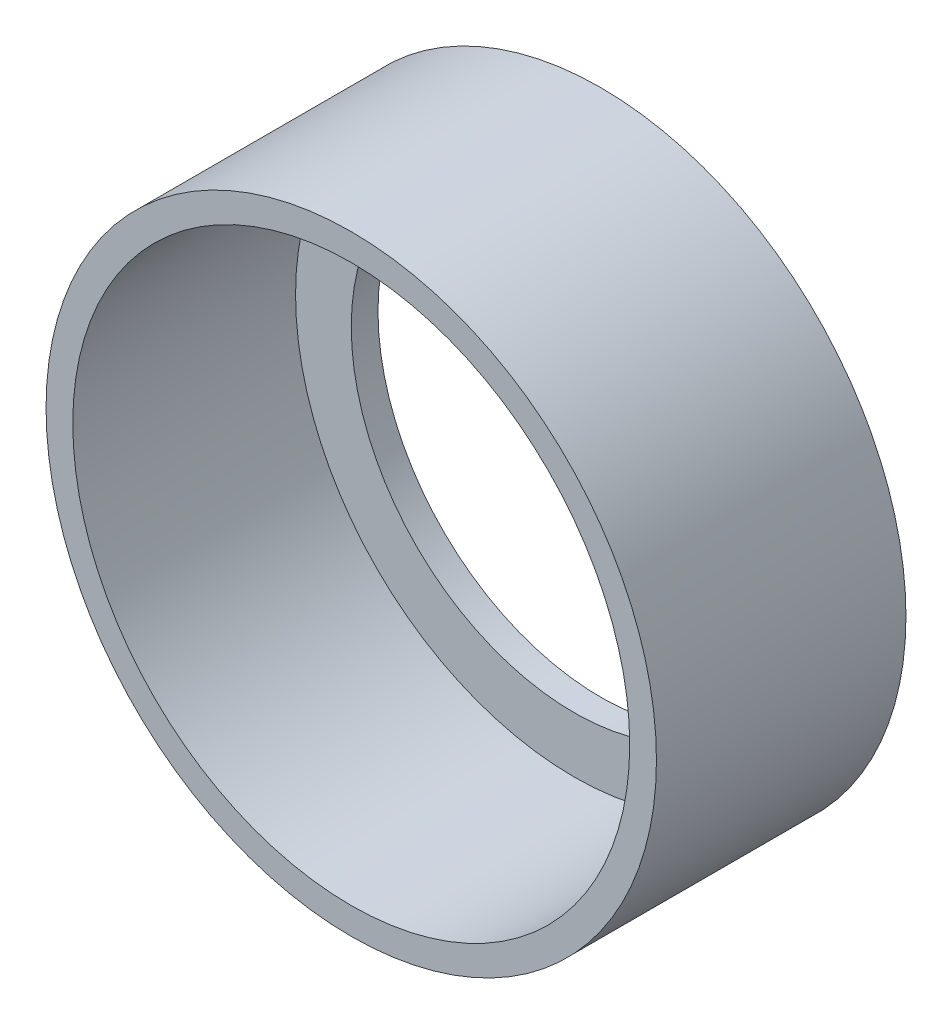
SolidWorks part; units mm, degrees
ref_plane "Front Plane" through (0, 0, 0) normal (0, 0, 1) x (1, 0, 0)
ref_plane "Top Plane" through (0, 0, 0) normal (0, 1, 0) x (1, 0, 0)
ref_plane "Right Plane" through (0, 0, 0) normal (1, 0, 0) x (0, 0, -1)
sketch "Sketch1" plane through (0, 0, 0) normal (0, 1, 0) x (1, 0, 0)
  line L0 (0, 10.179) -> (0, 0) construction
  line L1 (15.875, 5.4256) -> (17.399, 5.4256)
  line L2 (17.399, 5.4256) -> (17.399, 19.6496)
  line L3 (17.399, 19.6496) -> (12.7, 19.6496)
  line L4 (12.7, 19.6496) -> (12.7, 18.1256)
  line L5 (12.7, 18.1256) -> (15.875, 18.1256)
  line L6 (15.875, 18.1256) -> (15.875, 5.4256)
  dimension "D1" = 1.524
  dimension "D2" = 15.875
  dimension "D3" = 12.7
  dimension "D4" = 1.524
  dimension "D5" = 12.7
revolve "Revolve1" add sketch "Sketch1" angle 360 about L0
